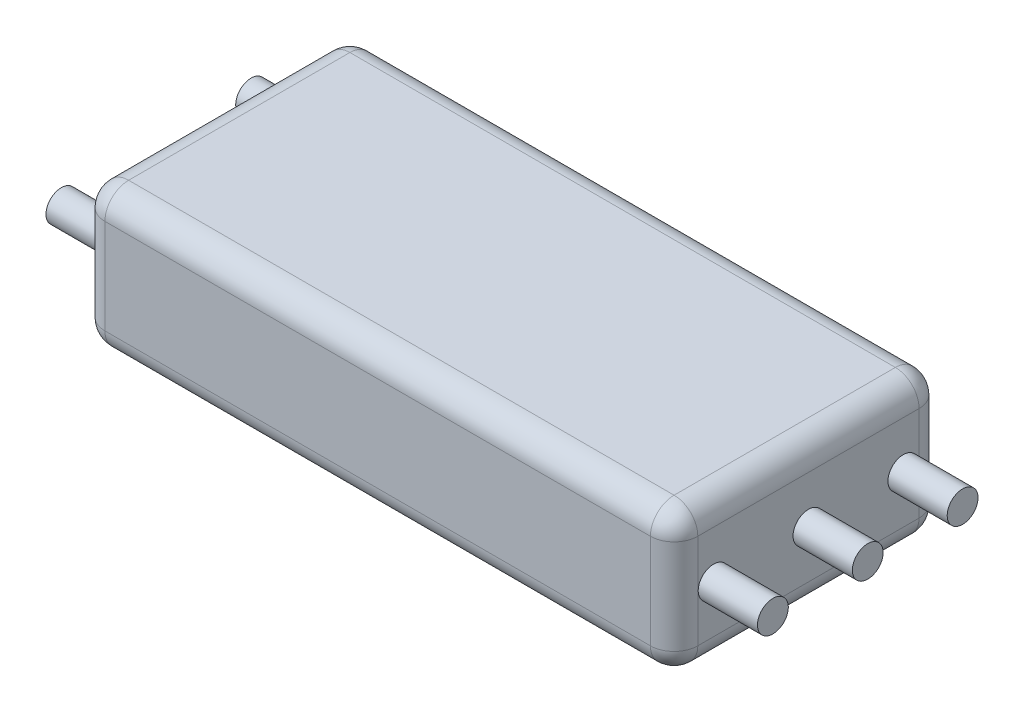
SolidWorks part; units mm, degrees
ref_plane "Front Plane" through (0, 0, 0) normal (0, 0, 1) x (1, 0, 0)
ref_plane "Top Plane" through (0, 0, 0) normal (0, 1, 0) x (1, 0, 0)
ref_plane "Right Plane" through (0, 0, 0) normal (1, 0, 0) x (0, 0, -1)
sketch "Sketch1" plane through (0, 0, 0) normal (0, 1, 0) x (1, 0, 0)
  line L1 (-31.75, -14.3891) -> (31.75, -14.3891)
  line L2 (-31.75, -14.3891) -> (-31.75, 14.3891)
  line L3 (-31.75, 14.3891) -> (31.75, 14.3891)
  line L4 (31.75, -14.3891) -> (31.75, 14.3891)
  line L5 (-31.75, -14.3891) -> (31.75, 14.3891) construction
  line L6 (-31.75, 14.3891) -> (31.75, -14.3891) construction
  point P0 (0, 0)
  dimension "D1" = 63.5
  dimension "D2" = 28.7782
extrude "Boss-Extrude1" add sketch "Sketch1" along normal mid plane 15.24
fillet "Fillet1" radius 2.54 12 edges at (31.75, 0, -14.3891) (-31.75, 0, -14.3891) (-31.75, 0, 14.3891) (31.75, 0, 14.3891) (0, 7.62, 14.3891) (-31.75, 7.62, 0) (0, 7.62, -14.3891) (31.75, 7.62, 0) (0, -7.62, -14.3891) (-31.75, -7.62, 0) (0, -7.62, 14.3891) (31.75, -7.62, 0)
sketch "Sketch2" plane through (0, 0, 0) normal (1, 0, 0) x (0, 0, -1)
  line L0 (0, 8.382) -> (0, -8.382) construction
  circle A0 centre (0, 0) radius 1.651
  circle A1 centre (10.16, 0) radius 1.651
  circle A2 centre (-10.16, 0) radius 1.651
  point P9 (10.16, -1.3222)
  dimension "D1" = 20.32
  dimension "D2" = 3.302
extrude "Boss-Extrude2" add sketch "Sketch2" along normal blind 6.35 from surface starting at face at (31.75, 0, 0)
extrude "Boss-Extrude3" add sketch "Sketch2<2>" against normal blind 6.35 from surface contours A1 | A2 starting at face at (-31.75, 0, 0)
sketch "Sketch2<2>" plane through (0, 0, 0) normal (1, 0, 0) x (0, 0, -1) same geometry as "Sketch2"
